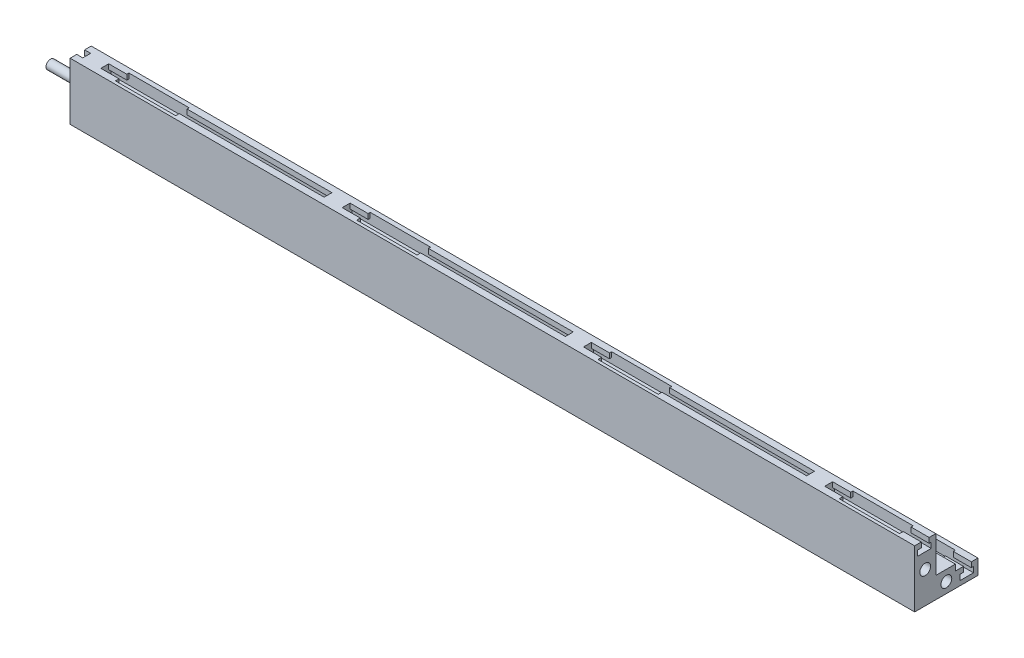
SolidWorks part; units mm, degrees
note: The reader was unsure of these and kept them because the rebuilt part matched: shared geometry of "Sketch1<5>".
ref_plane "Front Plane" through (0, 0, 0) normal (0, 0, 1) x (1, 0, 0)
ref_plane "Top Plane" through (0, 0, 0) normal (0, 1, 0) x (1, 0, 0)
ref_plane "Right Plane" through (0, 0, 0) normal (1, 0, 0) x (0, 0, -1)
sketch "Sketch1" plane through (-58.1463, 0, 0) normal (1, 0, 0) x (0, 0, -1)
  line L1 (-13.5289, 87.3403) -> (-24.0289, 87.3403)
  line L2 (-50.0289, 87.3403) -> (-18.5289, 87.3403) construction
  line L3 (-24.0289, 87.3403) -> (-24.0289, 76.8403)
  line L4 (-24.0289, 76.8403) -> (-13.5289, 76.8403)
  line L5 (-13.5289, 82.3403) -> (-13.5289, 22.3403) construction
  line L7 (-13.5289, 76.8403) -> (-13.5289, 87.3403)
  line L8 (-20.5289, 87.3403) -> (-20.5289, 80.3403)
  line L9 (-20.5289, 80.3403) -> (-13.5289, 80.3403)
  line L19 (-15.9289, 80.3403) -> (-15.9289, 78.4903)
  line L20 (-15.9289, 78.4903) -> (-17.0289, 78.4903)
  line L21 (-17.0289, 78.4903) -> (-17.0289, 77.5903)
  line L22 (-17.0289, 77.5903) -> (-13.5289, 77.5903)
  line L23 (-13.5289, 77.5903) -> (-13.5289, 78.4903)
  line L24 (-13.5289, 78.4903) -> (-14.6289, 78.4903)
  line L25 (-14.6289, 78.4903) -> (-14.6289, 80.3403)
  line L26 (-14.2789, 78.4903) -> (-14.2789, 77.5903)
  line L27 (-16.5289, 78.4903) -> (-16.5289, 77.5903)
  line L28 (-24.0289, 83.8403) -> (-20.5289, 83.8403)
  line L29 (-17.0289, 80.3403) -> (-17.0289, 76.8403)
  line L30 (-17.0289, 79.3403) -> (-13.5289, 79.3403)
  line L31 (-22.9289, 87.3403) -> (-22.9289, 85.4903)
  line L32 (-22.9289, 85.4903) -> (-24.0289, 85.4903)
  line L33 (-24.0289, 84.5903) -> (-20.5289, 84.5903)
  line L34 (-20.5289, 85.4903) -> (-21.6289, 85.4903)
  line L35 (-21.6289, 85.4903) -> (-21.6289, 87.3403)
  line L36 (-21.2789, 85.4903) -> (-21.2789, 84.5903)
  line L37 (-23.5289, 85.4903) -> (-23.5289, 84.5903)
  line L38 (-24.0289, 87.3403) -> (-24.0289, 83.8403)
  line L39 (-24.0289, 86.3403) -> (-20.5289, 86.3403)
  circle A0 centre (-22.2789, 82.0903) radius 0.75
  circle A1 centre (-18.7789, 78.5903) radius 0.75
  circle A2 centre (-22.2789, 82.0903) radius 0.9
  circle A3 centre (-18.7789, 78.5903) radius 0.9
  point P67 (0, 0)
  point P68 (0, 0)
  point P69 (0, 0)
  point P70 (0, 0)
  point P71 (0, 0)
  point P72 (0, 0)
  point P73 (0, 0)
  point P74 (0, 0)
  point P75 (0, 0)
  point P76 (0, 0)
  point P77 (-18.4603, 82.5648)
  dimension "D5" = 1.5
  dimension "D6" = 1.8
  dimension "D7" = 1.5
  dimension "D8" = 1.8
  dimension "D1" = 10.5
  dimension "D2" = 10.5
  dimension "D3" = 1.75
  dimension "D4" = 5.25
  dimension "D9" = 1.75
  dimension "D10" = 5.25
  dimension "D11" = 3.5
  dimension "D12" = 3.5
  dimension "D13" = 3.5
  dimension "D14" = 0.75
  dimension "D15" = 1.85
  dimension "D16" = 1.85
  dimension "D17" = 3.5
  dimension "D18" = 3.5
  dimension "D19" = 1.1
  dimension "D20" = 1.1
  dimension "D21" = 3.5
  dimension "D22" = 0.9
  dimension "D23" = 0.9
  dimension "D24" = 1.1
  dimension "D25" = 1.1
  dimension "D26" = 0
  dimension "D27" = 0.9
  dimension "D28" = 0.9
  dimension "D29" = 0.5
  dimension "D30" = 0.75
  dimension "D31" = 3.5
  dimension "D32" = 3.5
  dimension "D33" = 1
  dimension "D34" = 0.5
  dimension "D35" = 0.75
  dimension "D36" = 0.75
  dimension "D37" = 0.85
extrude "Boss-Extrude1" add sketch "Sketch1" along normal blind 140
extrude "Boss-Extrude2" add sketch "Sketch1<5>" against normal blind 5 contours A0 | A1
sketch "Sketch1<5>" plane through (-58.1463, 0, 0) normal (1, 0, 0) x (0, 0, -1) same geometry as "Sketch1"
sketch "Sketch2" plane through (81.8537, 0, 0) normal (1, 0, 0) x (0, 0, -1)
  line L0 (-13.5289, 87.3403) -> (-24.0289, 87.3403)
  line L1 (-24.0289, 87.3403) -> (-24.0289, 76.8403)
  line L2 (-24.0289, 76.8403) -> (-13.5289, 76.8403)
  line L3 (-13.5289, 76.8403) -> (-13.5289, 87.3403)
  line L4 (-20.5289, 87.3403) -> (-20.5289, 80.3403)
  line L5 (-20.5289, 80.3403) -> (-13.5289, 80.3403)
  line L6 (-24.0289, 84.8403) -> (-22.7789, 84.8403)
  line L7 (-22.7789, 84.8403) -> (-22.7789, 85.8403)
  line L8 (-22.7789, 85.8403) -> (-23.5289, 85.8403)
  line L9 (-23.5289, 85.8403) -> (-23.5289, 86.5903)
  line L10 (-23.5289, 86.5903) -> (-21.0289, 86.5903)
  line L11 (-21.0289, 86.5903) -> (-21.0289, 85.8403)
  line L12 (-21.0289, 85.8403) -> (-21.7789, 85.8403)
  line L13 (-21.7789, 85.8403) -> (-21.7789, 84.8403)
  line L14 (-21.7789, 84.8403) -> (-20.5289, 84.8403)
  line L15 (-15.9289, 80.3403) -> (-15.9289, 78.4903)
  line L16 (-15.9289, 78.4903) -> (-17.0289, 78.4903)
  line L17 (-17.0289, 78.4903) -> (-17.0289, 77.5903)
  line L18 (-17.0289, 77.5903) -> (-13.5289, 77.5903)
  line L19 (-13.5289, 77.5903) -> (-13.5289, 78.4903)
  line L20 (-13.5289, 78.4903) -> (-14.6289, 78.4903)
  line L21 (-14.6289, 78.4903) -> (-14.6289, 80.3403)
  line L22 (-13.8789, 78.4903) -> (-13.8789, 77.5903)
  line L23 (-16.6789, 78.4903) -> (-16.6789, 77.5903)
  line L24 (-24.0289, 83.8403) -> (-20.5289, 83.8403)
  line L25 (-17.0289, 80.3403) -> (-17.0289, 76.8403)
  line L26 (-17.0289, 79.3403) -> (-13.5289, 79.3403)
  circle A0 centre (-22.2789, 82.0903) radius 0.75
  circle A1 centre (-18.7789, 78.5903) radius 0.75
  circle A2 centre (-22.2789, 82.0903) radius 0.9
  circle A3 centre (-18.7789, 78.5903) radius 0.9
  dimension "D11" = 1.5
  dimension "D12" = 1.8
  dimension "D15" = 1.5
  dimension "D16" = 1.8
  dimension "D1" = 10.5
  dimension "D2" = 10.5
  dimension "D3" = 0.75
  dimension "D4" = 0.5
  dimension "D5" = 0.5
  dimension "D6" = 1.25
  dimension "D7" = 1.25
  dimension "D8" = 1
  dimension "D9" = 1.75
  dimension "D10" = 1.75
  dimension "D13" = 1.75
  dimension "D14" = 1.75
  dimension "D17" = 3.5
  dimension "D18" = 3.5
  dimension "D19" = 3.5
  dimension "D20" = 0.75
  dimension "D21" = 0.35
  dimension "D22" = 0.35
  dimension "D23" = 1.1
  dimension "D24" = 1.1
  dimension "D25" = 1
  dimension "D26" = 0.75
  dimension "D27" = 0.75
  dimension "D28" = 1
  dimension "D29" = 1
  dimension "D30" = 0.85
  dimension "D31" = 0.85
  dimension "D32" = 2.8
  dimension "D33" = 0
extrude "Cut-Extrude1" cut sketch "Sketch2" against normal blind 6 contours A0 | A2 A0 | A1 | A3 A1
sketch "Sketch3" plane through (81.8537, 0, 0) normal (1, 0, 0) x (0, 0, -1)
  line L0 (-17.0289, 80.3403) -> (-17.0289, 79.3403)
  line L1 (-20.5289, 80.3403) -> (-13.5289, 80.3403) construction
  line L2 (-17.0289, 79.3403) -> (-17.2789, 79.3403)
  line L3 (-17.2789, 79.3403) -> (-17.2789, 80.3403)
  line L4 (-17.2789, 80.3403) -> (-17.0289, 80.3403)
  dimension "D1" = 0.25
extrude "Cut-Extrude2" cut sketch "Sketch3" against normal through all
sketch "Sketch4" plane through (0, 84.5903, 0) normal (0, 1, 0) x (1, 0, 0)
  line L1 (68.8537, -21.2789) -> (68.8537, -23.5289)
  line L2 (81.8537, -23.5289) -> (-58.1463, -23.5289) construction
  line L6 (81.8537, -21.2789) -> (-58.1463, -21.2789) construction
  line L7 (78.8537, -21.2789) -> (78.8537, -23.5289)
  line L8 (78.8537, -23.5289) -> (68.8537, -23.5289)
  line L9 (68.8537, -21.2789) -> (78.8537, -21.2789)
  line L10 (28.8537, -21.2789) -> (28.8537, -23.5289)
  line L11 (28.8537, -21.2789) -> (38.8537, -21.2789)
  line L12 (38.8537, -21.2789) -> (38.8537, -23.5289)
  line L13 (38.8537, -23.5289) -> (28.8537, -23.5289)
  line L14 (-11.1463, -21.2789) -> (-11.1463, -23.5289)
  line L15 (-11.1463, -21.2789) -> (-1.1463, -21.2789)
  line L16 (-1.1463, -21.2789) -> (-1.1463, -23.5289)
  line L17 (-1.1463, -23.5289) -> (-11.1463, -23.5289)
  line L18 (-51.1463, -21.2789) -> (-51.1463, -23.5289)
  line L19 (-51.1463, -21.2789) -> (-41.1463, -21.2789)
  line L20 (-41.1463, -21.2789) -> (-41.1463, -23.5289)
  line L21 (-41.1463, -23.5289) -> (-51.1463, -23.5289)
  line L22 (68.8537, -21.2789) -> (28.8537, -21.2789) construction
  line L23 (81.8537, -23.5289) -> (81.8537, -21.2789) construction
  point P0 (78.7327, -21.2789)
  dimension "D1" = 10
  dimension "D3" = 40
  dimension "D4" = 3
  dimension "D2" = 4
extrude "Cut-Extrude3" cut sketch "Sketch4" along normal through all
sketch "Sketch6" plane through (0, 77.5903, 0) normal (0, 1, 0) x (1, 0, 0)
  line L16 (68.8537, -16.5289) -> (68.8537, -14.2789)
  line L19 (81.8537, -16.5289) -> (-58.1463, -16.5289) construction
  line L20 (81.8537, -14.2789) -> (-58.1463, -14.2789) construction
  line L21 (68.8537, -14.2789) -> (78.8537, -14.2789)
  line L22 (78.8537, -14.2789) -> (78.8537, -16.5289)
  line L23 (78.8537, -16.5289) -> (68.8537, -16.5289)
  line L24 (81.8537, -16.5289) -> (81.8537, -14.2789) construction
  line L25 (28.8537, -16.5289) -> (28.8537, -14.2789)
  line L26 (28.8537, -14.2789) -> (38.8537, -14.2789)
  line L27 (38.8537, -14.2789) -> (38.8537, -16.5289)
  line L28 (38.8537, -16.5289) -> (28.8537, -16.5289)
  line L29 (-11.1463, -16.5289) -> (-11.1463, -14.2789)
  line L30 (-11.1463, -14.2789) -> (-1.1463, -14.2789)
  line L31 (-1.1463, -14.2789) -> (-1.1463, -16.5289)
  line L32 (-1.1463, -16.5289) -> (-11.1463, -16.5289)
  line L33 (-51.1463, -16.5289) -> (-51.1463, -14.2789)
  line L34 (-51.1463, -14.2789) -> (-41.1463, -14.2789)
  line L35 (-41.1463, -14.2789) -> (-41.1463, -16.5289)
  line L36 (-41.1463, -16.5289) -> (-51.1463, -16.5289)
  line L37 (68.8537, -16.5289) -> (28.8537, -16.5289) construction
  dimension "D1" = 3
  dimension "D2" = 10
  dimension "D4" = 40
  dimension "D3" = 4
extrude "Cut-Extrude4" cut sketch "Sketch6" along normal through all
sketch "Sketch7" plane through (0, 77.5903, 0) normal (0, 1, 0) x (1, 0, 0)
  line L0 (-54.1463, -14.2789) -> (-57.1463, -14.2789)
  line L1 (-51.1463, -14.2789) -> (-58.1463, -14.2789) construction
  line L2 (-57.1463, -14.2789) -> (-57.1463, -16.5289)
  line L3 (-51.1463, -16.5289) -> (-58.1463, -16.5289) construction
  line L4 (-57.1463, -16.5289) -> (-54.1463, -16.5289)
  line L5 (-54.1463, -16.5289) -> (-54.1463, -14.2789)
  line L7 (-51.1463, -16.5289) -> (-51.1463, -15.9289) construction
  line L8 (-14.1463, -14.2789) -> (-17.1463, -14.2789)
  line L9 (-17.1463, -14.2789) -> (-17.1463, -16.5289)
  line L10 (-17.1463, -16.5289) -> (-14.1463, -16.5289)
  line L11 (-14.1463, -16.5289) -> (-14.1463, -14.2789)
  line L12 (25.8537, -14.2789) -> (22.8537, -14.2789)
  line L13 (22.8537, -14.2789) -> (22.8537, -16.5289)
  line L14 (22.8537, -16.5289) -> (25.8537, -16.5289)
  line L15 (25.8537, -16.5289) -> (25.8537, -14.2789)
  line L16 (65.8537, -14.2789) -> (62.8537, -14.2789)
  line L17 (62.8537, -14.2789) -> (62.8537, -16.5289)
  line L18 (62.8537, -16.5289) -> (65.8537, -16.5289)
  line L19 (65.8537, -16.5289) -> (65.8537, -14.2789)
  line L20 (-54.1463, -14.2789) -> (-14.1463, -14.2789) construction
  dimension "D1" = 3
  dimension "D2" = 3
  dimension "D4" = 40
  dimension "D3" = 4
extrude "Boss-Extrude3" add sketch "Sketch7" along normal up to surface (1.75 mm away) up to face at (13.4537, 79.3403, 14.3789)
sketch "Sketch8" plane through (0, 84.5903, 0) normal (0, 1, 0) x (1, 0, 0)
  line L0 (-54.1463, -21.2789) -> (-57.1463, -21.2789)
  line L1 (-51.1463, -21.2789) -> (-58.1463, -21.2789) construction
  line L2 (-57.1463, -21.2789) -> (-57.1463, -23.5289)
  line L3 (-51.1463, -23.5289) -> (-58.1463, -23.5289) construction
  line L4 (-57.1463, -23.5289) -> (-54.1463, -23.5289)
  line L5 (-54.1463, -23.5289) -> (-54.1463, -21.2789)
  line L6 (-51.1463, -23.5289) -> (-51.1463, -22.9289) construction
  line L7 (-14.1463, -21.2789) -> (-17.1463, -21.2789)
  line L8 (-17.1463, -21.2789) -> (-17.1463, -23.5289)
  line L9 (-17.1463, -23.5289) -> (-14.1463, -23.5289)
  line L10 (-14.1463, -23.5289) -> (-14.1463, -21.2789)
  line L11 (25.8537, -21.2789) -> (22.8537, -21.2789)
  line L12 (22.8537, -21.2789) -> (22.8537, -23.5289)
  line L13 (22.8537, -23.5289) -> (25.8537, -23.5289)
  line L14 (25.8537, -23.5289) -> (25.8537, -21.2789)
  line L15 (65.8537, -21.2789) -> (62.8537, -21.2789)
  line L16 (62.8537, -21.2789) -> (62.8537, -23.5289)
  line L17 (62.8537, -23.5289) -> (65.8537, -23.5289)
  line L18 (65.8537, -23.5289) -> (65.8537, -21.2789)
  line L19 (-54.1463, -21.2789) -> (-14.1463, -21.2789) construction
  dimension "D1" = 3
  dimension "D2" = 3
  dimension "D4" = 40
  dimension "D3" = 4
extrude "Boss-Extrude4" add sketch "Sketch8" along normal up to surface (1.75 mm away) up to face at (13.4537, 86.3403, 23.2789)
